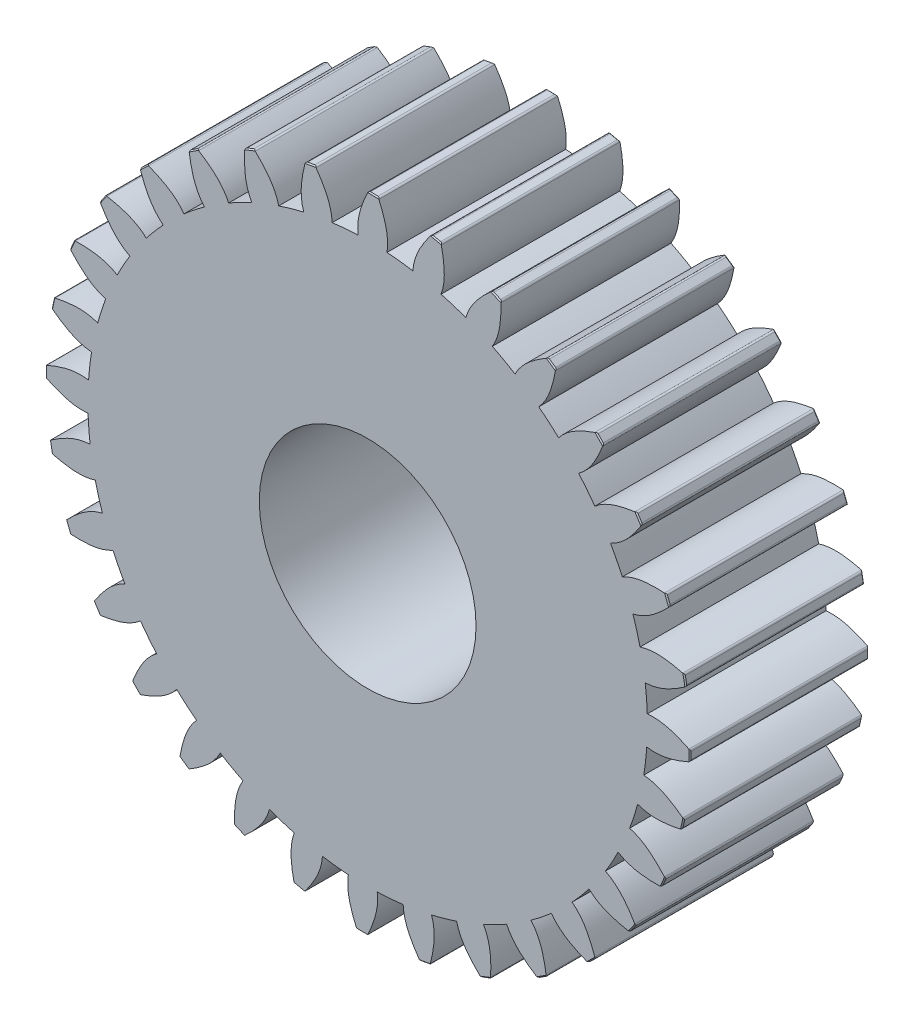
SolidWorks part; units mm, degrees
ref_plane "Front Plane" through (0, 0, 0) normal (0, 0, 1) x (1, 0, 0)
ref_plane "Top Plane" through (0, 0, 0) normal (0, 1, 0) x (1, 0, 0)
ref_plane "Right Plane" through (0, 0, 0) normal (1, 0, 0) x (0, 0, -1)
sketch "Sketch1" plane through (0, 0, 0) normal (0, 0, 1) x (1, 0, 0)
  line L0 (-12.1833, 51.9659) -> (-9.4579, 52.3144) construction
  line L1 (-1.282, 53.3596) -> (9.6736, 52.4911) construction
  line L2 (9.6736, 52.4911) -> (20.2192, 49.3971) construction
  line L3 (20.2192, 49.3971) -> (29.9075, 44.209) construction
  line L4 (-1.282, 53.3596) -> (-12.2688, 53.0956) construction
  line L5 (9.6736, 52.4911) -> (-11.9423, 56.4747) construction
  line L6 (20.2192, 49.3971) -> (-10.2937, 61.8866) construction
  line L7 (29.9075, 44.209) -> (-6.5034, 68.841) construction
  line L8 (0, 0) -> (-6.5467, 51.2082) construction
  line L9 (-12.1833, 51.9659) -> (-9.4579, 52.3144)
  line L10 (0, 0) -> (-9.4579, 52.3144) construction
  circle A0 centre (0, 0) radius 53.375
  arc A1 (-9.6686, 58.7092) -> (-11.4997, 58.3781) centre (0, 0) ccw
  circle A2 centre (0, 0) radius 56 construction
  circle A3 centre (0, 0) radius 51.625
  spline S0 degree 3 poles (-11.7948, 50.2596) (-11.9828, 50.8237) (-12.1907, 51.7673) (-12.342, 53.8476) (-12.0772, 56.0109) (-11.6707, 57.75) (-11.4997, 58.3781) knots -0.095364 -0.095364 -0.095364 -0.095364 0 0.062574 0.250076 0.357807 0.357807 0.357807 0.357807
  spline S1 degree 3 poles (-6.5495, 51.2079) (-6.571, 51.8021) (-6.7066, 52.7587) (-7.2933, 54.7604) (-8.2988, 56.694) (-9.2884, 58.1807) (-9.6686, 58.7092) knots -0.095364 -0.095364 -0.095364 -0.095364 0 0.062574 0.250076 0.357807 0.357807 0.357807 0.357807
  dimension "D1" = 119
  dimension "D2" = 112
  dimension "D3" = 106.75
  dimension "D4" = 103.25
  dimension "D5" = 10.99
  dimension "D6" = 10.99
  dimension "D7" = 21.98
  dimension "D8" = 32.97
  dimension "D9" = 43.96
extrude "Boss-Extrude1" add sketch "Sketch1" along normal blind 32.97
chamfer "Chamfer1" distance 0.2 angle 45 2 edges at (-10.5854, 58.5508, 32.97) (-10.5854, 58.5508, 0)
fillet "Fillet1" radius 0.4 2 edges at (-11.4997, 58.3781, 16.485) (-9.6686, 58.7092, 16.485)
pattern_circular "CirPattern1" count 32 over 360 of "Boss-Extrude1", "Chamfer1", "Fillet1"
sketch "Sketch2" plane through (0, 0, 0) normal (0, 0, -1) x (-1, 0, 0)
  circle A0 centre (0, 0) radius 20
  dimension "D1" = 40
extrude "Cut-Extrude1" cut sketch "Sketch2" against normal through all
